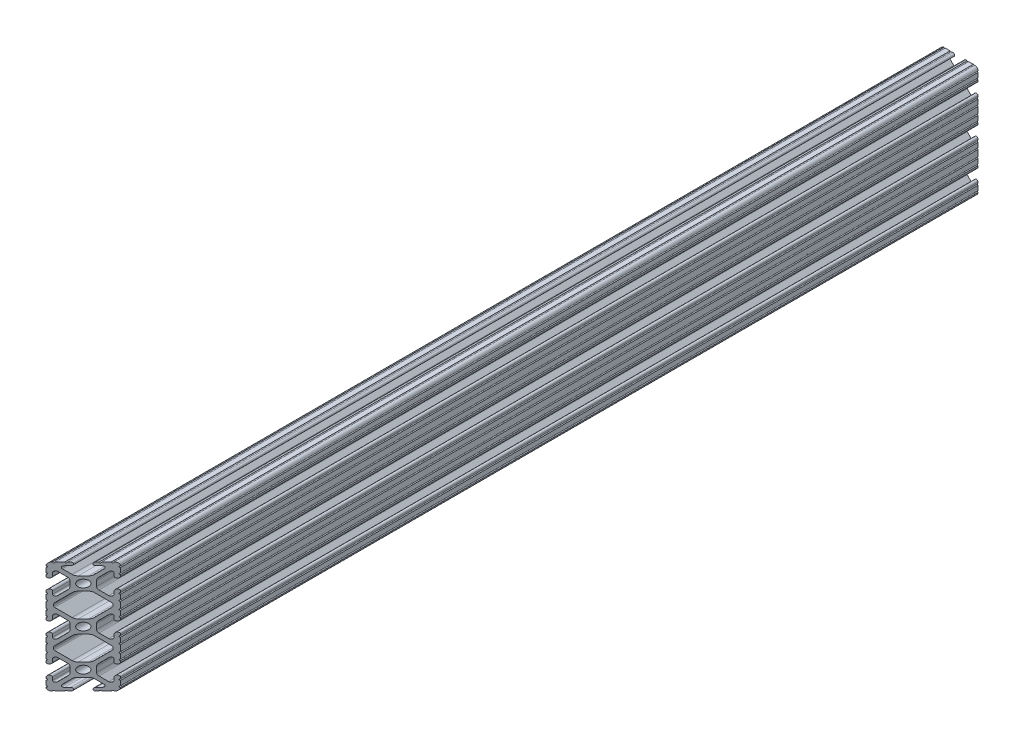
SolidWorks part; units mm, degrees
ref_plane "Front Plane" through (0, 0, 0) normal (0, 0, 1) x (1, 0, 0)
ref_plane "Top Plane" through (0, 0, 0) normal (0, 1, 0) x (1, 0, 0)
ref_plane "Right Plane" through (0, 0, 0) normal (1, 0, 0) x (0, 0, -1)
sketch "Sketch1" plane through (0, 0, 0) normal (0, 0, 1) x (1, 0, 0)
  line L0 (-12.7, 0) -> (12.7, 0) construction
  line L1 (-10.16, 13.1469) -> (-10.16, 12.2531)
  line L2 (-3.8143, 20.0397) -> (-9.7731, 14.0808)
  line L3 (0, 20.8915) -> (-1.7578, 20.8915)
  line L7 (-1.7578, 4.5085) -> (0, 4.5085)
  line L8 (-9.7731, 11.3192) -> (-3.8143, 5.3603)
  line L9 (-6.3246, 38.1) -> (-9.5504, 38.1)
  line L10 (-12.7, 34.8742) -> (-12.7, 31.7246)
  line L11 (-12.7, 30.7086) -> (-12.7, 29.7561)
  line L12 (-10.4902, 29.7561) -> (-10.4902, 31.7602)
  line L13 (-8.6864, 32.5073) -> (-5.3603, 29.1812)
  line L14 (-4.5085, 27.1248) -> (-4.5085, 23.6752)
  line L15 (-5.3603, 21.6188) -> (-8.6864, 18.2927)
  line L16 (-10.4902, 19.0398) -> (-10.4902, 21.0439)
  line L17 (-12.7, 21.0439) -> (-12.7, 20.0914)
  line L18 (-12.7, 19.0754) -> (-12.7, 15.8496)
  line L19 (-12.7, 14.8336) -> (-12.7, 10.5664)
  line L20 (-12.7, 9.5504) -> (-12.7, 6.3246)
  line L21 (-12.7, 5.3086) -> (-12.7, 4.3561)
  line L22 (-10.4902, 4.3561) -> (-10.4902, 6.3602)
  line L23 (-8.6864, 7.1073) -> (-5.3603, 3.7812)
  line L24 (-4.5085, 1.7248) -> (-4.5085, 0)
  line L25 (-11.5951, 28.6512) -> (-11.5951, 22.1488) construction
  line L26 (-11.5951, 25.4) -> (0, 25.4) construction
  line L27 (-12.7, 31.7246) -> (-6.3246, 38.1) construction
  line L28 (-12.7, 12.7) -> (0, 12.7) construction
  line L29 (-9.4336, 32.8168) -> (0, 32.8168) construction
  line L30 (-9.4336, 17.9832) -> (0, 17.9832) construction
  line L31 (-9.4336, 32.8168) -> (-9.4336, 17.9832) construction
  line L44 (0, 29.9085) -> (-1.7578, 29.9085)
  line L45 (-3.8143, 30.7603) -> (-7.1404, 34.0864)
  line L46 (-6.3932, 35.8902) -> (-4.3561, 35.8902)
  line L47 (-4.3561, 38.1) -> (-5.3086, 38.1)
  line L48 (0, 0) -> (0, 38.1) construction
  arc A0 (0, 28.0035) -> (0, 22.7965) centre (0, 25.4) ccw
  arc A1 (0, 2.6035) -> (-2.6035, 0) centre (0, 0) ccw
  arc A2 (-9.7731, 14.0808) -> (-10.16, 13.1469) centre (-8.8392, 13.1469) ccw
  arc A3 (-1.7578, 20.8915) -> (-3.8143, 20.0397) centre (-1.7578, 17.9832) ccw
  arc A8 (-3.8143, 5.3603) -> (-1.7578, 4.5085) centre (-1.7578, 7.4168) ccw
  arc A9 (-10.16, 12.2531) -> (-9.7731, 11.3192) centre (-8.8392, 12.2531) ccw
  arc A10 (-6.3246, 38.1) -> (-5.3086, 38.1) centre (-5.8166, 38.1) ccw
  arc A11 (-10.5664, 38.1) -> (-9.5504, 38.1) centre (-10.0584, 38.1) ccw
  arc A12 (-10.5664, 38.1) -> (-12.7, 35.8902) centre (-10.4888, 35.8902) ccw
  arc A13 (-12.7, 34.8742) -> (-12.7, 35.8902) centre (-12.7, 35.3822) ccw
  arc A14 (-12.7, 30.7086) -> (-12.7, 31.7246) centre (-12.7, 31.2166) ccw
  arc A15 (-12.7, 29.7561) -> (-10.4902, 29.7561) centre (-11.5951, 29.7561) ccw
  arc A16 (-8.6864, 32.5073) -> (-10.4902, 31.7602) centre (-9.4336, 31.7602) ccw
  arc A17 (-4.5085, 27.1248) -> (-5.3603, 29.1812) centre (-7.4168, 27.1248) ccw
  arc A18 (-5.3603, 21.6188) -> (-4.5085, 23.6752) centre (-7.4168, 23.6752) ccw
  arc A19 (-10.4902, 19.0398) -> (-8.6864, 18.2927) centre (-9.4336, 19.0398) ccw
  arc A20 (-10.4902, 21.0439) -> (-12.7, 21.0439) centre (-11.5951, 21.0439) ccw
  arc A21 (-12.7, 19.0754) -> (-12.7, 20.0914) centre (-12.7, 19.5834) ccw
  arc A22 (-12.7, 14.8336) -> (-12.7, 15.8496) centre (-12.7, 15.3416) ccw
  arc A23 (-12.7, 9.5504) -> (-12.7, 10.5664) centre (-12.7, 10.0584) ccw
  arc A24 (-12.7, 5.3086) -> (-12.7, 6.3246) centre (-12.7, 5.8166) ccw
  arc A25 (-12.7, 4.3561) -> (-10.4902, 4.3561) centre (-11.5951, 4.3561) ccw
  arc A26 (-8.6864, 7.1073) -> (-10.4902, 6.3602) centre (-9.4336, 6.3602) ccw
  arc A27 (-4.5085, 1.7248) -> (-5.3603, 3.7812) centre (-7.4168, 1.7248) ccw
  circle A28 centre (0, 25.4) radius 2.6035 construction
  arc A49 (-3.8143, 30.7603) -> (-1.7578, 29.9085) centre (-1.7578, 32.8168) ccw
  arc A50 (-6.3932, 35.8902) -> (-7.1404, 34.0864) centre (-6.3932, 34.8336) ccw
  arc A51 (-4.3561, 35.8902) -> (-4.3561, 38.1) centre (-4.3561, 36.9951) ccw
  point P53 (-9.4336, 25.4)
  point P63 (-0.8789, 20.8915)
  dimension "D16" = 0.508
  dimension "D99" = 2.6035
  dimension "D27" = 1.0566
  dimension "D28" = 1.3208
  dimension "Center Hole Diameter" = 5.207
  dimension "Rail Height" = 76.2
  dimension "Rail Width" = 25.4
  dimension "D3" = 2.2098
  dimension "D4" = 2.2098
  dimension "D5" = 2.2098
  dimension "D6" = 25.4
  dimension "D7" = 9.017
  dimension "D8" = 9.017
  dimension "T-slot Width" = 6.5024
  dimension "D9" = 2.2098
  dimension "D10" = 9.017
  dimension "D11" = 9.017
  dimension "D12" = 6.5024
  dimension "D13" = 6.5024
  dimension "D14" = 10.5664
  dimension "D15" = 5.3086
  dimension "D17" = 2.2098
  dimension "D18" = 16.383
  dimension "D2" = 45
  dimension "D20" = 45
  dimension "D21" = 45
  dimension "D22" = 2.54
  dimension "D23" = 25.4
  dimension "D24" = 4.2672
  dimension "D25" = 12.7508
  dimension "D26" = 14.8336
  dimension "T-slot Depth" = 8.1915
sketch "Sketch2" plane through (0, 0, 0) normal (1, 0, 0) x (0, 0, -1)
  line L0 (-304.8, 0) -> (304.8, 0)
  point P2 (-241.3, 0)
  point P3 (241.3, 0)
  dimension "Length" = 609.6
  dimension "D1" = 63.5
  dimension "D2" = 63.5
sketch "Sketch3" plane through (0, 0, 0) normal (0, 0, 1) x (1, 0, 0)
  line L0 (-4.5085, 1.7248) -> (-4.5085, 0) construction
  line L1 (-8.6864, 7.1073) -> (-5.3603, 3.7812) construction
  line L2 (-10.4902, 4.3561) -> (-10.4902, 6.3602) construction
  line L3 (-12.7, 5.3086) -> (-12.7, 4.3561) construction
  line L4 (-12.7, 9.5504) -> (-12.7, 6.3246) construction
  line L5 (-12.7, 14.8336) -> (-12.7, 10.5664) construction
  line L6 (-12.7, 19.0754) -> (-12.7, 15.8496) construction
  line L7 (-12.7, 21.0439) -> (-12.7, 20.0914) construction
  line L8 (-10.4902, 19.0398) -> (-10.4902, 21.0439) construction
  line L9 (-5.3603, 21.6188) -> (-8.6864, 18.2927) construction
  line L10 (-4.5085, 27.1248) -> (-4.5085, 23.6752) construction
  line L11 (-8.6864, 32.5073) -> (-5.3603, 29.1812) construction
  line L12 (-10.4902, 29.7561) -> (-10.4902, 31.7602) construction
  line L13 (-12.7, 30.7086) -> (-12.7, 29.7561) construction
  line L14 (-12.7, 34.8742) -> (-12.7, 31.7246) construction
  line L15 (-6.3246, 38.1) -> (-9.5504, 38.1) construction
  line L16 (-4.3561, 38.1) -> (-5.3086, 38.1) construction
  line L17 (-6.3932, 35.8902) -> (-4.3561, 35.8902) construction
  line L18 (-3.8143, 30.7603) -> (-7.1404, 34.0864) construction
  line L19 (0, 29.9085) -> (-1.7578, 29.9085) construction
  line L20 (-1.7578, 4.5085) -> (0, 4.5085) construction
  line L21 (-9.7731, 11.3192) -> (-3.8143, 5.3603) construction
  line L22 (-10.16, 13.1469) -> (-10.16, 12.2531) construction
  line L23 (-3.8143, 20.0397) -> (-9.7731, 14.0808) construction
  line L24 (0, 20.8915) -> (-1.7578, 20.8915) construction
  line L25 (-4.5085, 1.7248) -> (-4.5085, 0)
  line L26 (-8.6864, 7.1073) -> (-5.3603, 3.7812)
  line L27 (-10.4902, 4.3561) -> (-10.4902, 6.3602)
  line L28 (-12.7, 5.3086) -> (-12.7, 4.3561)
  line L29 (-12.7, 9.5504) -> (-12.7, 6.3246)
  line L30 (-12.7, 14.8336) -> (-12.7, 10.5664)
  line L31 (-12.7, 19.0754) -> (-12.7, 15.8496)
  line L32 (-12.7, 21.0439) -> (-12.7, 20.0914)
  line L33 (-10.4902, 19.0398) -> (-10.4902, 21.0439)
  line L34 (-5.3603, 21.6188) -> (-8.6864, 18.2927)
  line L35 (-4.5085, 27.1248) -> (-4.5085, 23.6752)
  line L36 (-8.6864, 32.5073) -> (-5.3603, 29.1812)
  line L37 (-10.4902, 29.7561) -> (-10.4902, 31.7602)
  line L38 (-12.7, 30.7086) -> (-12.7, 29.7561)
  line L39 (-12.7, 34.8742) -> (-12.7, 31.7246)
  line L40 (-6.3246, 38.1) -> (-9.5504, 38.1)
  line L41 (-4.3561, 38.1) -> (-5.3086, 38.1)
  line L42 (-6.3932, 35.8902) -> (-4.3561, 35.8902)
  line L43 (-3.8143, 30.7603) -> (-7.1404, 34.0864)
  line L44 (0, 29.9085) -> (-1.7578, 29.9085)
  line L45 (-1.7578, 4.5085) -> (0, 4.5085)
  line L46 (-9.7731, 11.3192) -> (-3.8143, 5.3603)
  line L47 (-10.16, 13.1469) -> (-10.16, 12.2531)
  line L48 (-3.8143, 20.0397) -> (-9.7731, 14.0808)
  line L49 (0, 20.8915) -> (-1.7578, 20.8915)
  line L50 (0, 29.9085) -> (0, 28.0035)
  line L51 (0, 22.7965) -> (0, 20.8915)
  line L52 (0, 4.5085) -> (0, 2.6035)
  line L53 (-4.5085, 0) -> (-2.6035, 0)
  arc A0 (-4.5085, 1.7248) -> (-5.3603, 3.7812) centre (-7.4168, 1.7248) ccw construction
  arc A1 (-8.6864, 7.1073) -> (-10.4902, 6.3602) centre (-9.4336, 6.3602) ccw construction
  arc A2 (-12.7, 4.3561) -> (-10.4902, 4.3561) centre (-11.5951, 4.3561) ccw construction
  arc A3 (-12.7, 5.3086) -> (-12.7, 6.3246) centre (-12.7, 5.8166) ccw construction
  arc A4 (-12.7, 9.5504) -> (-12.7, 10.5664) centre (-12.7, 10.0584) ccw construction
  arc A5 (-12.7, 14.8336) -> (-12.7, 15.8496) centre (-12.7, 15.3416) ccw construction
  arc A6 (-12.7, 19.0754) -> (-12.7, 20.0914) centre (-12.7, 19.5834) ccw construction
  arc A7 (-10.4902, 21.0439) -> (-12.7, 21.0439) centre (-11.5951, 21.0439) ccw construction
  arc A8 (-10.4902, 19.0398) -> (-8.6864, 18.2927) centre (-9.4336, 19.0398) ccw construction
  arc A9 (-5.3603, 21.6188) -> (-4.5085, 23.6752) centre (-7.4168, 23.6752) ccw construction
  arc A10 (-4.5085, 27.1248) -> (-5.3603, 29.1812) centre (-7.4168, 27.1248) ccw construction
  arc A11 (-8.6864, 32.5073) -> (-10.4902, 31.7602) centre (-9.4336, 31.7602) ccw construction
  arc A12 (-12.7, 29.7561) -> (-10.4902, 29.7561) centre (-11.5951, 29.7561) ccw construction
  arc A13 (-12.7, 30.7086) -> (-12.7, 31.7246) centre (-12.7, 31.2166) ccw construction
  arc A14 (-12.7, 34.8742) -> (-12.7, 35.8902) centre (-12.7, 35.3822) ccw construction
  arc A15 (-10.5664, 38.1) -> (-12.7, 35.8902) centre (-10.4888, 35.8902) ccw construction
  arc A16 (-10.5664, 38.1) -> (-9.5504, 38.1) centre (-10.0584, 38.1) ccw construction
  arc A17 (-6.3246, 38.1) -> (-5.3086, 38.1) centre (-5.8166, 38.1) ccw construction
  arc A18 (-4.3561, 35.8902) -> (-4.3561, 38.1) centre (-4.3561, 36.9951) ccw construction
  arc A19 (-6.3932, 35.8902) -> (-7.1404, 34.0864) centre (-6.3932, 34.8336) ccw construction
  arc A20 (-3.8143, 30.7603) -> (-1.7578, 29.9085) centre (-1.7578, 32.8168) ccw construction
  arc A21 (-3.8143, 5.3603) -> (-1.7578, 4.5085) centre (-1.7578, 7.4168) ccw construction
  arc A22 (-10.16, 12.2531) -> (-9.7731, 11.3192) centre (-8.8392, 12.2531) ccw construction
  arc A23 (-9.7731, 14.0808) -> (-10.16, 13.1469) centre (-8.8392, 13.1469) ccw construction
  arc A24 (-1.7578, 20.8915) -> (-3.8143, 20.0397) centre (-1.7578, 17.9832) ccw construction
  arc A25 (0, 2.6035) -> (-2.6035, 0) centre (0, 0) ccw construction
  arc A26 (0, 28.0035) -> (0, 22.7965) centre (0, 25.4) ccw construction
  arc A27 (-4.5085, 1.7248) -> (-5.3603, 3.7812) centre (-7.4168, 1.7248) ccw
  arc A28 (-8.6864, 7.1073) -> (-10.4902, 6.3602) centre (-9.4336, 6.3602) ccw
  arc A29 (-12.7, 4.3561) -> (-10.4902, 4.3561) centre (-11.5951, 4.3561) ccw
  arc A30 (-12.7, 5.3086) -> (-12.7, 6.3246) centre (-12.7, 5.8166) ccw
  arc A31 (-12.7, 9.5504) -> (-12.7, 10.5664) centre (-12.7, 10.0584) ccw
  arc A32 (-12.7, 14.8336) -> (-12.7, 15.8496) centre (-12.7, 15.3416) ccw
  arc A33 (-12.7, 19.0754) -> (-12.7, 20.0914) centre (-12.7, 19.5834) ccw
  arc A34 (-10.4902, 21.0439) -> (-12.7, 21.0439) centre (-11.5951, 21.0439) ccw
  arc A35 (-10.4902, 19.0398) -> (-8.6864, 18.2927) centre (-9.4336, 19.0398) ccw
  arc A36 (-5.3603, 21.6188) -> (-4.5085, 23.6752) centre (-7.4168, 23.6752) ccw
  arc A37 (-4.5085, 27.1248) -> (-5.3603, 29.1812) centre (-7.4168, 27.1248) ccw
  arc A38 (-8.6864, 32.5073) -> (-10.4902, 31.7602) centre (-9.4336, 31.7602) ccw
  arc A39 (-12.7, 29.7561) -> (-10.4902, 29.7561) centre (-11.5951, 29.7561) ccw
  arc A40 (-12.7, 30.7086) -> (-12.7, 31.7246) centre (-12.7, 31.2166) ccw
  arc A41 (-12.7, 34.8742) -> (-12.7, 35.8902) centre (-12.7, 35.3822) ccw
  arc A42 (-10.5664, 38.1) -> (-12.7, 35.8902) centre (-10.4888, 35.8902) ccw
  arc A43 (-10.5664, 38.1) -> (-9.5504, 38.1) centre (-10.0584, 38.1) ccw
  arc A44 (-6.3246, 38.1) -> (-5.3086, 38.1) centre (-5.8166, 38.1) ccw
  arc A45 (-4.3561, 35.8902) -> (-4.3561, 38.1) centre (-4.3561, 36.9951) ccw
  arc A46 (-6.3932, 35.8902) -> (-7.1404, 34.0864) centre (-6.3932, 34.8336) ccw
  arc A47 (-3.8143, 30.7603) -> (-1.7578, 29.9085) centre (-1.7578, 32.8168) ccw
  arc A48 (-3.8143, 5.3603) -> (-1.7578, 4.5085) centre (-1.7578, 7.4168) ccw
  arc A49 (-10.16, 12.2531) -> (-9.7731, 11.3192) centre (-8.8392, 12.2531) ccw
  arc A50 (-9.7731, 14.0808) -> (-10.16, 13.1469) centre (-8.8392, 13.1469) ccw
  arc A51 (-1.7578, 20.8915) -> (-3.8143, 20.0397) centre (-1.7578, 17.9832) ccw
  arc A52 (0, 2.6035) -> (-2.6035, 0) centre (0, 0) ccw
  arc A53 (0, 28.0035) -> (0, 22.7965) centre (0, 25.4) ccw
extrude "Boss-Extrude1" add sketch "Sketch3" along normal mid plane 609.6
mirror "Mirror1" about plane through (0, 0, 0) normal (1, 0, 0) of bodies 104
mirror "Mirror2" about plane through (0, 0, 0) normal (0, 1, 0) of bodies 105
sketch "Sketch9" plane through (0, 0, 0) normal (0, 1, 0) x (1, 0, 0)
  line L0 (-12.7, -304.8) -> (12.7, -279.4)
  line L1 (12.7, -279.4) -> (12.954, -279.4)
  line L2 (12.954, -279.4) -> (12.954, -305.054)
  line L3 (12.954, -305.054) -> (-12.7, -305.054)
  line L4 (-12.7, -305.054) -> (-12.7, -304.8)
  line L5 (12.7, -304.8) -> (12.7, 304.8) construction
  line L6 (-2.6035, -304.8) -> (2.6035, -304.8) construction
  point P5 (0, 0)
  point P6 (13.4099, -331.5747)
  point P7 (-12.244, -331.3176)
  point P8 (0, 0)
  point P9 (0, 0)
  point P10 (16.3759, -302.3675)
  point P11 (0, 0)
  point P12 (0, 0)
  point P13 (0, 0)
  point P14 (0, 0)
  point P15 (0, 0)
  point P16 (0, 0)
  point P17 (0, 0)
  point P18 (0, 0)
  point P19 (0, 0)
  point P20 (0, 0)
  point P21 (0, 0)
  point P22 (0, 0)
  point P23 (0, 0)
  point P24 (0, 0)
  point P27 (0, 0)
  point P28 (0, 0)
  point P31 (0, 0)
  dimension "D2" = 25.654
  dimension "D3" = 0.254
extrude "Cut-Extrude1" cut sketch "Sketch9" against normal blind 38.1 and the other way blind 38.1
sketch "Sketch12" plane through (0, 0, 0) normal (0, 1, 0) x (1, 0, 0)
  line L0 (0, -292.0579) -> (2.2633, -289.8312)
  line L5 (0, -292.0579) -> (-4.8117, -287.1671)
  line L6 (2.2633, -289.8312) -> (-0.4586, -287.0646)
  line L7 (-4.8117, -287.1671) -> (-2.2082, -284.6057)
  line L8 (-0.4586, -287.0646) -> (1.7619, -284.88)
  line L10 (1.7619, -284.88) -> (-0.3279, -282.7559)
  line L11 (-2.2082, -284.6057) -> (-0.3279, -282.7559)
  point P0 (0, 0)
  dimension "D1" = 3.175
equation "\"D3@Sketch1\" = \"Rail Width@Sketch1\" * 0.0870in"
equation "\"D4@Sketch1\"=\"D3@Sketch1\""
equation "\"D5@Sketch1\"=\"D3@Sketch1\""
equation "\"D6@Sketch1\" = \"Rail Width@Sketch1\""
equation "\"D7@Sketch1\" = \"Rail Width@Sketch1\" * 0.3550in"
equation "\"D8@Sketch1\"=\"D7@Sketch1\""
equation "\"D9@Sketch1\"=\"D4@Sketch1\""
equation "\"D10@Sketch1\"=\"D8@Sketch1\""
equation "\"D11@Sketch1\"=\"D7@Sketch1\""
equation "\"D12@Sketch1\"=\"T-slot Width@Sketch1\""
equation "\"D14@Sketch1\" = \"Rail Width@Sketch1\" * 0.4160in"
equation "\"D15@Sketch1\" = \"Rail Width@Sketch1\" * 0.2090in"
equation "\"D16@Sketch1\" = \"Rail Width@Sketch1\" * 0.0200in"
equation "\"D17@Sketch1\"=\"D9@Sketch1\""
equation "\"D18@Sketch1\" = \"Rail Width@Sketch1\" * 0.6450in"
equation "\"D99@Sketch1\" = \"Rail Width@Sketch1\" * 0.1025in"
equation "\"D22@Sketch1\"=\"Rail Width@Sketch1\"*0.10"
equation "\"D23@Sketch1\"=\"Rail Width@Sketch1\""
equation "\"D24@Sketch1\"=\"Rail Width@Sketch1\"*0.1680in"
equation "\"D25@Sketch1\"=\"Rail Width@Sketch1\"*0.5020in"
equation "\"D26@Sketch1\"=\"Rail Width@Sketch1\"*0.584"
equation "\"D27@Sketch1\"=\"Rail Width@Sketch1\"*0.0416in"
equation "\"D28@Sketch1\"=\"Rail Width@Sketch1\"*0.052"
equation "\"D1@Boss-Extrude1\" = \"Length@Sketch2\""
equation "\"D2@Sketch2\"=\"D1@Sketch2\""
equation "\"D13@Sketch1\"=\"T-slot Width@Sketch1\""
equation "\"D1@Sketch12\"=.125in"
